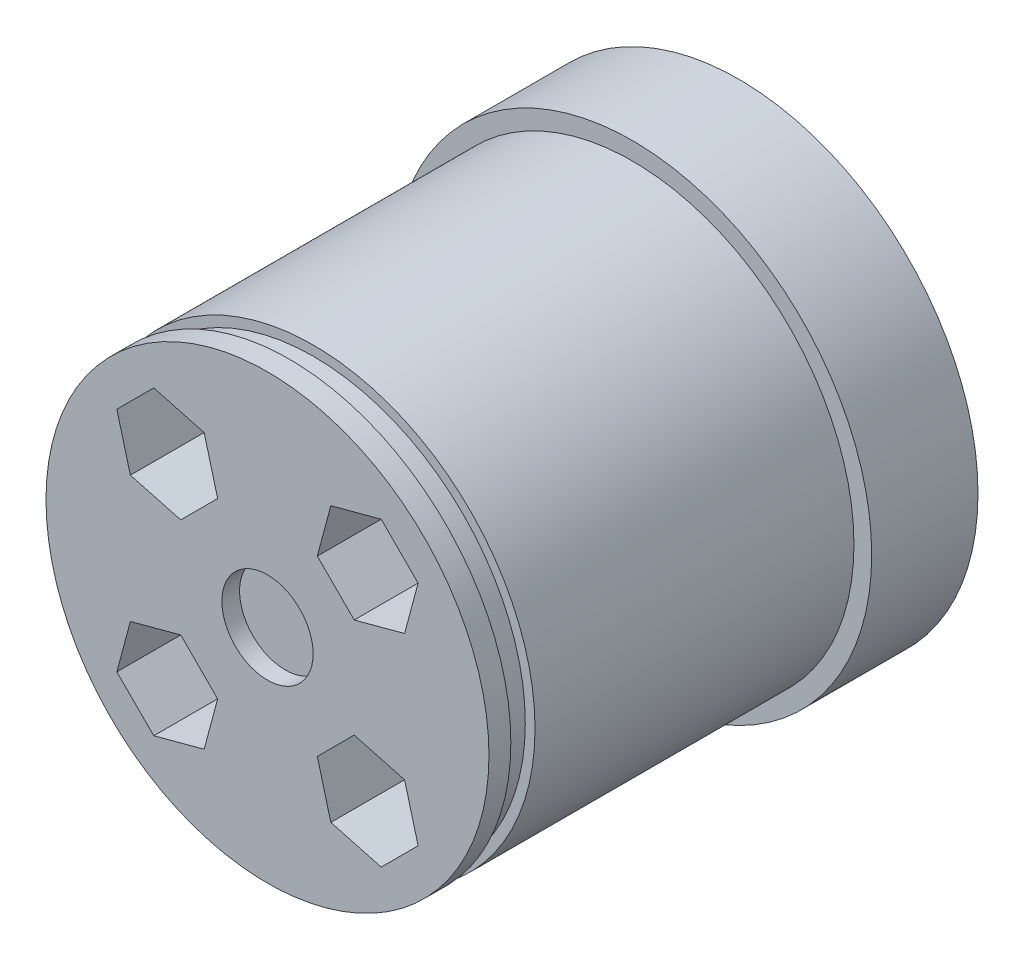
SolidWorks part; units mm, degrees
ref_plane "Front Plane" through (0, 0, 0) normal (0, 0, 1) x (1, 0, 0)
ref_plane "Top Plane" through (0, 0, 0) normal (0, 1, 0) x (1, 0, 0)
ref_plane "Right Plane" through (0, 0, 0) normal (1, 0, 0) x (0, 0, -1)
ref_axis "Z" through (0, 0, 21.93) along (0, 0, -1)
sketch "Sketch1" plane through (0, 0, 0) normal (0, 0, 1) x (1, 0, 0)
  circle A0 centre (0, 0) radius 12.5
  dimension "D1" = 25
extrude "Boss-Extrude1" add sketch "Sketch1" along normal blind 20.6
sketch "Sketch2" plane through (0, 0, 0) normal (0, 0, 1) x (1, 0, 0)
  circle A0 centre (0, 0) radius 13.5
  dimension "D1" = 27
extrude "Boss-Extrude2" add sketch "Sketch2" against normal blind 6
sketch "Sketch9" plane through (0, 0, 0) normal (1, 0, 0) x (0, 0, -1)
  line L0 (0, 0) -> (-18, 0) construction
  line L1 (-18, 0) -> (-18, -12.5) construction
  line L2 (-18, -12.5) -> (-19.365, -12.5)
  line L3 (-19.365, -12.5) -> (-19.365, -11.95)
  line L4 (-19.365, -11.95) -> (-18, -11.95)
  line L5 (-18, -11.95) -> (-18, -12.5)
  dimension "D1" = 18
  dimension "D2" = 25
  dimension "D3" = 1.365
  dimension "D4" = 23.9
revolve "Cut-Revolve1" cut sketch "Sketch9" angle 360 about axis through (0, 0, 21.93) along (0, 0, -1)
sketch "Sketch4" plane through (0, 0, 20.6) normal (0, 0, 1) x (1, 0, 0)
  circle A0 centre (0, 0) radius 2.575
  dimension "D1" = 5.15
extrude "MagnetSlot" cut sketch "Sketch4" against normal blind 1
sketch "Sketch6" plane through (0, 0, 20.6) normal (0, 0, 1) x (1, 0, 0)
  line L0 (0, 0) -> (5.6569, 5.6569) construction
  line L1 (0, 0) -> (0, 18.4845) construction
  line L2 (6.4189, 8.501) -> (3.5748, 7.7389)
  line L3 (3.5748, 7.7389) -> (2.8127, 4.8948)
  line L4 (2.8127, 4.8948) -> (4.8948, 2.8127)
  line L5 (4.8948, 2.8127) -> (7.7389, 3.5748)
  line L6 (7.7389, 3.5748) -> (8.501, 6.4189)
  line L7 (8.501, 6.4189) -> (6.4189, 8.501)
  circle A0 centre (5.6569, 5.6569) radius 2.55 construction
  dimension "D1" = 8
  dimension "D2" = 5.1
  dimension "D3" = 45
extrude "NutCut" cut sketch "Sketch6" against normal offset from surface (22.6 mm away) 4 up to face at (13.5, 0, -6)
sketch "Sketch8" plane through (0, 0, 20.6) normal (0, 0, 1) x (1, 0, 0)
  circle A0 centre (5.6569, 5.6569) radius 1.35
  dimension "D1" = 2.7
extrude "ScrewHole" cut sketch "Sketch8" against normal through all both and the other way through all
pattern_circular "CirPattern1" count 4 over 360 about axis through (0, 0, 21.93) along (0, 0, -1) of "MagnetSlot", "NutCut", "ScrewHole"
equation "\"BearingBaseDistance\"= 10"
equation "\"BearingOD\"= 32"
equation "\"BearingHeight\"= 4"
equation "\"SeatsOD\"= \"BearingOD\" + 10"
equation "\"WireHarnessHeight\"= 4"
equation "\"OuterWallWidth\"= 6"
equation "\"OverallOD\" = 45"
equation "\"RetainingRingThickness\" = 1.30"
equation "\"RetaininRingGrooveDiameter\" = 23.9"
equation "\"ShaftLengthAfterFlange\" = 2*\"BearingHeight\" + \"BearingBaseDistance\" + \"RetainingRingThickness\"*2\t'give a retaining ring thickness of extra clearance"
equation "\"RetainingRingGrooveBase\" = \"ShaftLengthAfterFlange\" - \"RetainingRingThickness\"*2"
equation "\"BearingID\" = 25"
equation "\"CoverClearance\" = 1"
equation "\"CoverThickness\" = 1"
equation "\"FlangHeight\" = \"CoverThickness\" + \"CoverClearance\" + \"WireHarnessHeight\""
equation "\"D1@Sketch1\"=\"BearingID\""
equation "\"D2@Sketch9\"=\"BearingID\""
equation "\"D3@Sketch9\"=\"RetainingRingThickness\"*1.05"
equation "\"D4@Sketch9\"=\"RetaininRingGrooveDiameter\""
equation "\"D1@Boss-Extrude2\"=\"FlangHeight\""
equation "\"D1@Sketch9\"=\"RetainingRingGrooveBase\""
equation "\"D1@Boss-Extrude1\"=\"ShaftLengthAfterFlange\""
equation "\"OuterHousingHeight\" = \"WireHarnessHeight\" + \"BearingHeight\"*2 + \"BearingBaseDistance\""
equation "\"PCBWidth\" = 5"
equation "\"PCBHeight\" = \"OuterHousingHeight\" "
equation "\"PCBThickness\" = 1"
equation "\"NormalDistSidewallPCBToZ\" = (\"OverallOD\"/2) - 1.6\t'radial distance from the z axis to pcb origin on the top/connector side"
equation "\"PCBSidewallCutoutClearance\" = 0.1"
equation "\"OutputHubBoltCircleRadius\" = 8"
equation "\"D1@Sketch6\"=\"OutputHubBoltCircleRadius\""
equation "\"OutputHubOD\" = 27"
equation "\"D1@Sketch2\"=\"OutputHubOD\""
